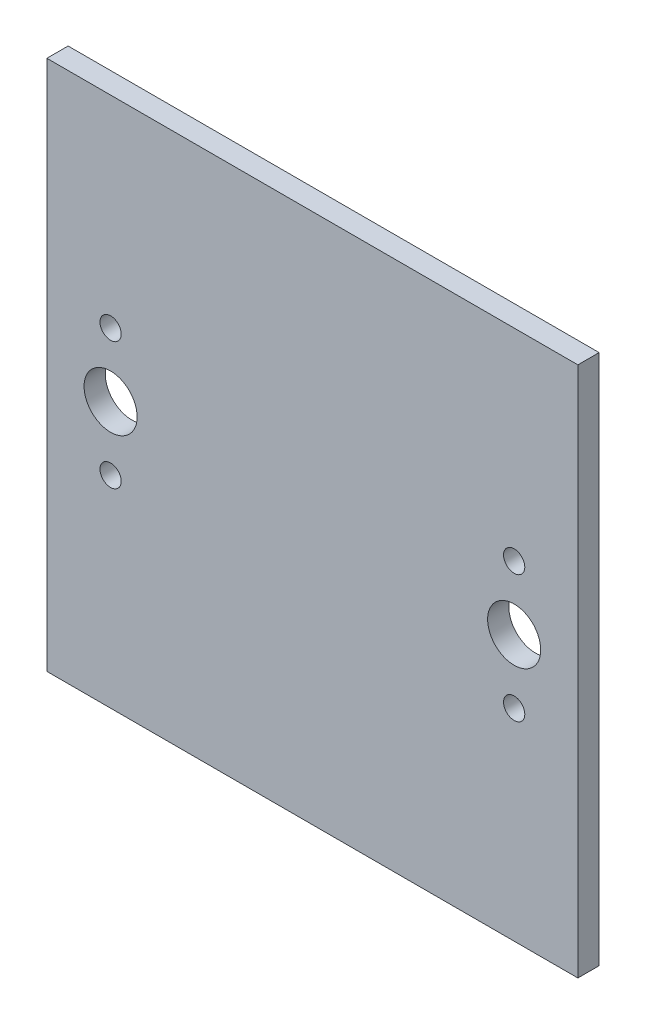
SolidWorks part; units mm, degrees
ref_plane "Front Plane" through (0, 0, 0) normal (0, 0, 1) x (1, 0, 0)
ref_plane "Top Plane" through (0, 0, 0) normal (0, 1, 0) x (1, 0, 0)
ref_plane "Right Plane" through (0, 0, 0) normal (1, 0, 0) x (0, 0, -1)
sketch "Sketch1" plane through (0, 0, 0) normal (0, 0, 1) x (1, 0, 0)
  line L1 (0, 0) -> (50, 0)
  line L2 (0, 0) -> (0, 50)
  line L3 (0, 50) -> (50, 50)
  line L4 (50, 0) -> (50, 50)
  dimension "D1" = 50
  dimension "D2" = 50
extrude "plate_body" add sketch "Sketch1" along normal blind 2
sketch "Sketch2" plane through (0, 0, 2) normal (0, 0, 1) x (1, 0, 0)
  line L0 (50, 50) -> (0, 50) construction
  line L1 (0, 50) -> (0, 0) construction
  circle A0 centre (6, 25) radius 2.5
  circle A1 centre (44, 25) radius 2.5
  dimension "D1" = 38
  dimension "D2" = 5
  dimension "D3" = 5
  dimension "D4" = 25
  dimension "D5" = 6
  dimension "D6" = 25
extrude "shaft_bearings" cut sketch "Sketch2" against normal through all
sketch "Sketch3" plane through (0, 0, 2) normal (0, 0, 1) x (1, 0, 0)
  line L0 (0, 50) -> (0, 0) construction
  line L1 (0, 50) -> (0, 0) construction
  line L2 (50, 0) -> (50, 50) construction
  circle A0 centre (6, 31) radius 1
  circle A1 centre (6, 19) radius 1
  circle A2 centre (44, 31) radius 1
  circle A3 centre (44, 19) radius 1
  circle A4 centre (6, 25) radius 2.5 construction
  circle A5 centre (44, 25) radius 2.5 construction
  dimension "D1" = 2
  dimension "D2" = 2
  dimension "D3" = 6
  dimension "D4" = 6
  dimension "D5" = 12
  dimension "D6" = 6
  dimension "D7" = 2
  dimension "D8" = 2
  dimension "D9" = 12
  dimension "D10" = 6
  dimension "D11" = 6
  dimension "D12" = 6
extrude "bearing_bolt_holes" cut sketch "Sketch3" against normal through all
